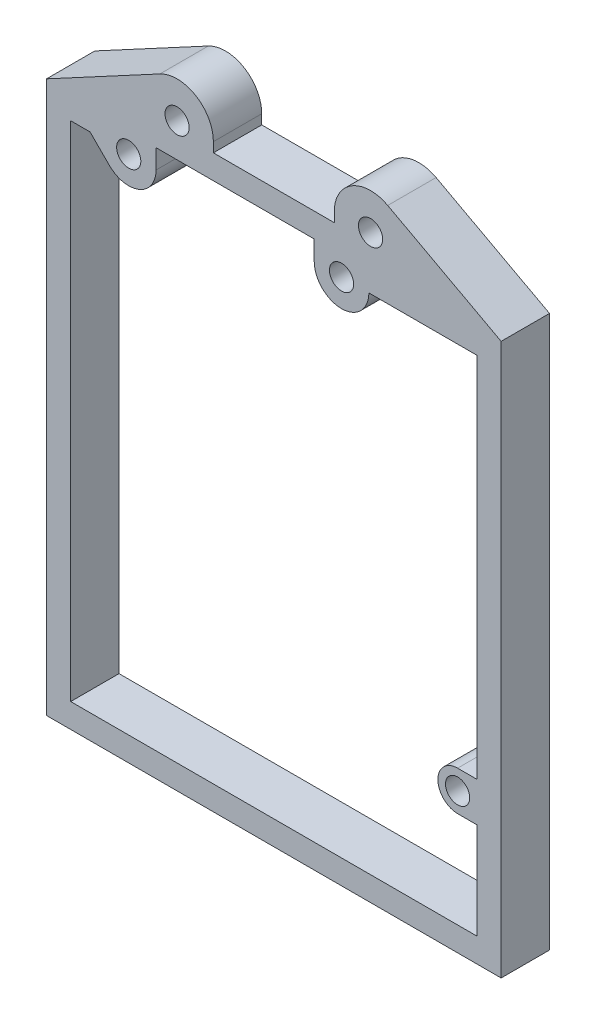
SolidWorks part; units mm, degrees
ref_plane "Front Plane" through (0, 0, 0) normal (0, 0, 1) x (1, 0, 0)
ref_plane "Top Plane" through (0, 0, 0) normal (0, 1, 0) x (1, 0, 0)
ref_plane "Right Plane" through (0, 0, 0) normal (1, 0, 0) x (0, 0, -1)
sketch "Sketch1" plane through (0, 0, 0) normal (0, 0, 1) x (1, 0, 0)
  line L0 (13.97, -3.175) -> (39.37, -3.175)
  line L2 (39.37, -3.175) -> (56.515, -3.175)
  line L3 (18.7325, 73.025) -> (18.7325, 71.755)
  line L4 (56.515, 69.215) -> (41.6251, 77.2198)
  line L5 (34.6075, 73.025) -> (34.6075, 71.755)
  line L6 (-3.175, 69.215) -> (11.7149, 77.2198)
  line L7 (34.6075, 71.755) -> (18.7325, 71.755)
  line L8 (0, 11.0938) -> (0, 16.5575)
  line L36 (53.34, 66.04) -> (53.34, 0) construction
  line L37 (53.34, 0) -> (0, 0) construction
  line L38 (0, 0) -> (0, 66.04) construction
  line L39 (0, 66.04) -> (2.54, 66.04) construction
  line L43 (40.386, 66.04) -> (53.34, 66.04) construction
  line L44 (-3.175, -3.175) -> (56.515, -3.175)
  line L45 (56.515, -3.175) -> (56.515, 69.215)
  line L46 (-3.175, 69.215) -> (-3.175, -3.175)
  line L47 (1.2249, 69.215) -> (-3.175, 69.215)
  line L48 (3.7649, 71.755) -> (1.2249, 69.215)
  line L49 (39.1611, 71.755) -> (3.7649, 71.755)
  line L50 (41.7011, 69.215) -> (39.1611, 71.755)
  line L51 (56.515, 69.215) -> (41.7011, 69.215)
  line L52 (-3.175, -3.175) -> (13.97, -3.175)
  line L53 (56.515, -3.175) -> (56.515, 69.215)
  line L54 (-3.175, 69.215) -> (-3.175, -3.175)
  line L60 (53.34, 66.04) -> (53.34, 17.8275)
  line L61 (53.34, 0) -> (0, 0)
  line L62 (0, 0) -> (0, 11.0938)
  line L63 (0, 66.04) -> (2.54, 66.04)
  line L64 (26.67, -3.175) -> (26.67, 77.2177) construction
  line L66 (11.2075, 68.58) -> (31.9725, 68.58)
  line L67 (40.386, 66.04) -> (53.34, 66.04)
  line L68 (50.8, 17.8275) -> (53.34, 17.8275)
  line L69 (50.8, 12.6525) -> (53.34, 12.6525)
  line L70 (53.34, 12.6525) -> (53.34, 0)
  line L74 (0, 16.5575) -> (0, 66.04)
  line L75 (5.08, 63.5065) -> (2.54, 66.04)
  line L76 (11.2075, 66.04) -> (11.2075, 68.58)
  line L77 (39.1475, 66.04) -> (40.386, 66.04)
  line L78 (31.9725, 66.04) -> (31.9725, 68.58)
  circle A0 centre (35.56, 66.04) radius 1.5875 construction
  circle A1 centre (7.62, 66.04) radius 1.5875 construction
  circle A3 centre (50.8, 15.24) radius 1.5875 construction
  circle A4 centre (35.56, 66.04) radius 1.5875
  circle A5 centre (7.62, 66.04) radius 1.5875
  circle A7 centre (50.8, 15.24) radius 1.5875
  arc A9 (50.8, 17.8275) -> (50.8, 12.6525) centre (50.8, 15.24) ccw
  arc A10 (5.08, 63.5065) -> (11.2075, 66.04) centre (7.62, 66.04) ccw
  arc A13 (31.9725, 66.04) -> (39.1475, 66.04) centre (35.56, 66.04) ccw
  circle A15 centre (35.56, 66.04) radius 3.5875 construction
  circle A16 centre (7.62, 66.04) radius 3.5875 construction
  circle A18 centre (39.37, 73.025) radius 1.5875
  arc A19 (41.6251, 77.2198) -> (34.6075, 73.025) centre (39.37, 73.025) ccw
  circle A20 centre (13.97, 73.025) radius 1.5875
  arc A22 (11.7149, 77.2198) -> (18.7325, 73.025) centre (13.97, 73.025) cw
  circle A24 centre (13.97, 73.025) radius 4.7625 construction
  point P20 (2.54, 13.97)
  point P29 (2.54, 13.97)
  point P34 (53.3875, 15.24)
  point P37 (6.1275, 13.97)
  point P41 (4.0581, 14.4341)
  point P47 (11.2075, 66.04)
  point P54 (39.1475, 66.04)
  point P58 (26.67, -9.525)
  point P64 (31.4325, -9.525)
  point P65 (26.67, -6.35)
  point P69 (26.67, 71.755)
  point P71 (39.37, 73.025)
  point P74 (50.4825, 73.025)
  point P75 (12.3825, 73.025)
  point P78 (31.4325, -6.35)
  dimension "D8" = 3.175
  dimension "D7" = 12.7
  dimension "D9" = 12.7
  dimension "D1" = 3.175
  dimension "D3" = 2
  dimension "D12" = 3.175
extrude "Boss-Extrude1" add sketch "Sketch1" along normal blind 6.35
